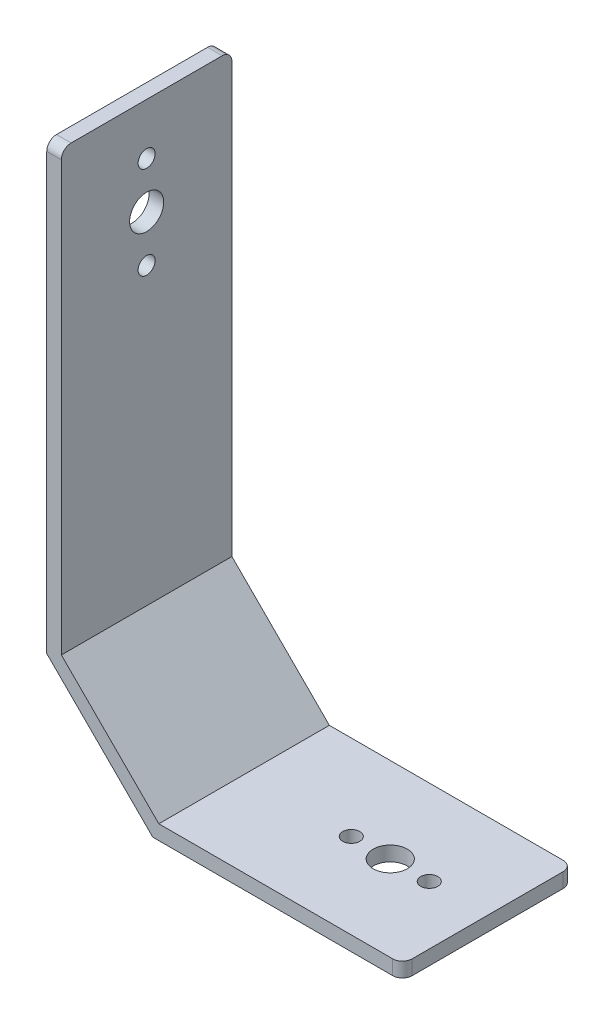
SolidWorks part; units mm, degrees
ref_plane "Plan de face" through (0, 0, 0) normal (0, 0, 1) x (1, 0, 0)
ref_plane "Plan de dessus" through (0, 0, 0) normal (0, 1, 0) x (1, 0, 0)
ref_plane "Plan de droite" through (0, 0, 0) normal (1, 0, 0) x (0, 0, -1)
sketch "Esquisse1" plane through (0, 0, 0) normal (0, 0, 1) x (1, 0, 0)
  line L0 (0, 0) -> (0, 90)
  line L1 (20, -20) -> (70, -20)
  line L2 (0, 0) -> (20, -20)
  dimension "D1" = 50
  dimension "D2" = 90
  dimension "D3" = 20
  dimension "D4" = 20
extrude "Extru.-Mince1" add sketch "Esquisse1" along normal blind 35 thin thin type one direction wall 3
sketch "Esquisse2" plane through (0, 0, 0) normal (1, 0, 0) x (0, 0, -1)
  line L0 (-36.8852, 70) -> (-4.765, 70) construction
  line L1 (-17.5, 88.5735) -> (-17.5, 46.5374) construction
  line L2 (0, 90) -> (0, 0) construction
  line L3 (-35, 90) -> (0, 90) construction
  circle A0 centre (-17.5, 79.5) radius 1.75
  circle A1 centre (-17.5, 60.5) radius 1.75
  circle A4 centre (-17.5, 70) radius 3.5
  dimension "D5" = 3.5
  dimension "D8" = 3.5
  dimension "D11" = 7
  dimension "D1" = 9.5
  dimension "D2" = 9.5
  dimension "D9" = 17.5
  dimension "D10" = 20
extrude "Enlèv. mat.-Extru.1" cut sketch "Esquisse2" against normal blind 3
fillet "Congé3" radius 2 1 edges at (-1.5, 90, 35)
fillet "Congé4" radius 2 1 edges at (-1.5, 90, 0)
fillet "Congé5" radius 2 1 edges at (70, -21.5, 35)
fillet "Congé6" radius 2 1 edges at (70, -21.5, 0)
sketch "Esquisse3" plane through (0, -20, 0) normal (0, 1, 0) x (1, 0, 0)
  line L0 (58, -17.5) -> (75.235, -17.5) construction
  line L1 (50, -7.5415) -> (50, -49.5776) construction
  line L2 (20, 0) -> (68, 0) construction
  line L3 (70, -33) -> (70, -2) construction
  circle A0 centre (58, -17.5) radius 1.75
  circle A1 centre (42, -17.5) radius 1.75
  circle A2 centre (50, -17.5) radius 3.5
  dimension "D3" = 3.5
  dimension "D4" = 3.5
  dimension "D5" = 7
  dimension "D1" = 8
  dimension "D2" = 8
  dimension "D6" = 17.5
  dimension "D7" = 20
extrude "Enlèv. mat.-Extru.2" cut sketch "Esquisse3" against normal blind 10
